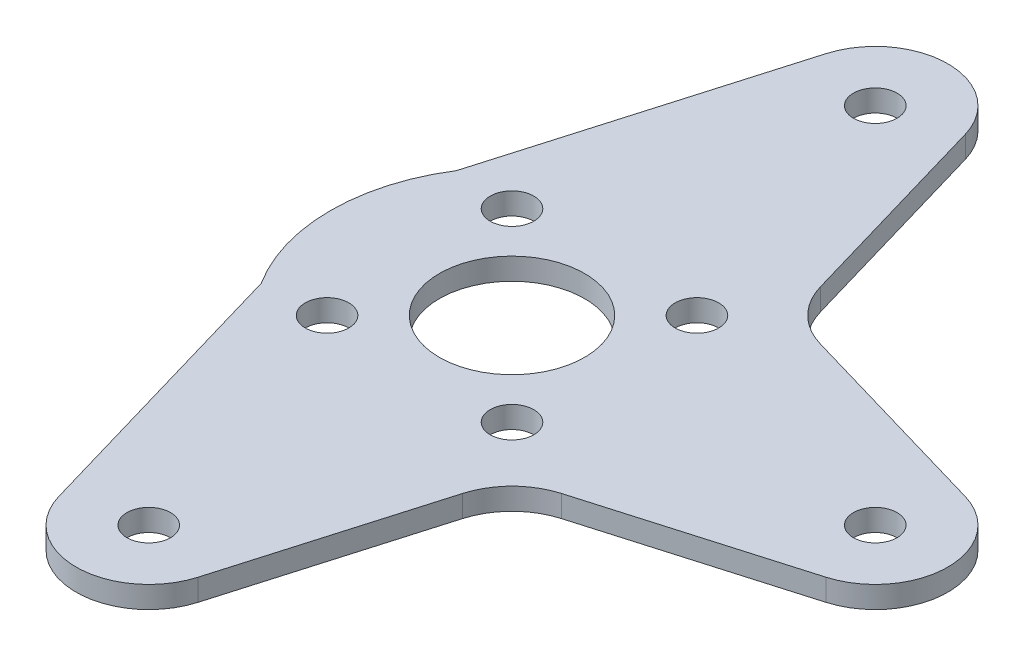
SolidWorks part; units mm, degrees
material "201 Stal nierdzewna odprężona (SS)"
ref_plane "Płaszczyzna przednia" through (0, 0, 0) normal (0, 0, 1) x (1, 0, 0)
ref_plane "Płaszczyzna górna" through (0, 0, 0) normal (0, 1, 0) x (1, 0, 0)
ref_plane "Płaszczyzna prawa" through (0, 0, 0) normal (1, 0, 0) x (0, 0, -1)
sketch "Szkic1" plane through (0, 0, 0) normal (0, 1, 0) x (1, 0, 0)
  line L4 (17.8194, -24.6194) -> (9.6, -52.8)
  line L5 (-21.08, -13.44) -> (-9.6, -52.8)
  line L6 (24.6194, -17.8194) -> (52.8, -9.6)
  line L7 (24.6194, 17.8194) -> (52.8, 9.6)
  line L8 (17.8194, 24.6194) -> (9.6, 52.8)
  line L9 (-21.08, 13.44) -> (-9.6, 52.8)
  arc A9 (-9.6, -52.8) -> (9.6, -52.8) centre (0, -50) ccw
  circle A10 centre (0, -50) radius 3
  arc A11 (24.6194, -17.8194) -> (17.8194, -24.6194) centre (27.4194, -27.4194) ccw
  arc A12 (52.8, -9.6) -> (52.8, 9.6) centre (50, 0) ccw
  arc A13 (17.8194, 24.6194) -> (24.6194, 17.8194) centre (27.4194, 27.4194) ccw
  arc A14 (9.6, 52.8) -> (-9.6, 52.8) centre (0, 50) ccw
  circle A15 centre (0, 50) radius 3
  circle A16 centre (-12.7279, 12.7279) radius 3
  circle A17 centre (-12.7279, -12.7279) radius 3
  circle A18 centre (12.7279, -12.7279) radius 3
  circle A19 centre (12.7279, 12.7279) radius 3
  circle A20 centre (50, 0) radius 3
  arc A21 (-21.08, 13.44) -> (-21.08, -13.44) centre (0, 0) ccw
  circle A22 centre (0, 0) radius 10
extrude "Dodanie-wyciągnięcie1" add sketch "Szkic1" along normal blind 3 contours L9 A21 L5 A9 L4 A11 L6 A12 L7 A13 L8 A14 A22 A10 A15 A16 A17 A18 A19 A20 region at (12.298, 0, 38.2979)
